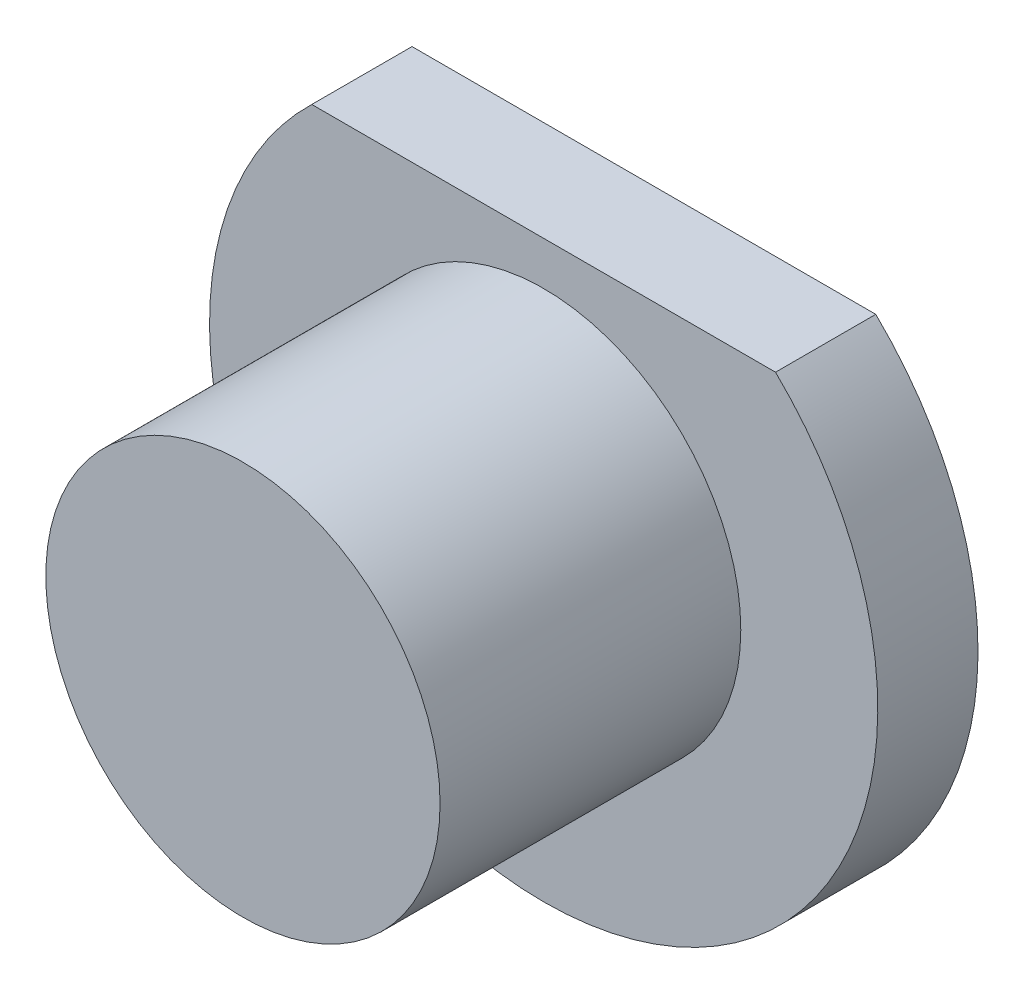
SolidWorks part; units mm, degrees
ref_plane "Front Plane" through (0, 0, 0) normal (0, 0, 1) x (1, 0, 0)
ref_plane "Top Plane" through (0, 0, 0) normal (0, 1, 0) x (1, 0, 0)
ref_plane "Right Plane" through (0, 0, 0) normal (1, 0, 0) x (0, 0, -1)
sketch "Sketch1" plane through (0, 0, 0) normal (0, 0, 1) x (1, 0, 0)
  line L2 (-3.4699, 3.6) -> (3.4699, 3.6)
  circle A0 centre (0, 0) radius 2.95
  arc A1 (-3.4699, 3.6) -> (3.4699, 3.6) centre (0, 0) ccw
extrude "Boss-Extrude1" add sketch "Sketch1" along normal blind 4.5 contours A0
extrude "Boss-Extrude2" add sketch "Sketch1<5>" against normal blind 1.5 separate body
sketch "Sketch1<5>" plane through (0, 0, 0) normal (0, 0, 1) x (1, 0, 0) same geometry as "Sketch1"
sketch "Sketch3" plane through (0, 0, 0) normal (0, 0, -1) x (-1, 0, 0)
  circle A0 centre (0, 0) radius 2.95
extrude "Boss-Extrude3" add sketch "Sketch3" along normal blind 1.5
